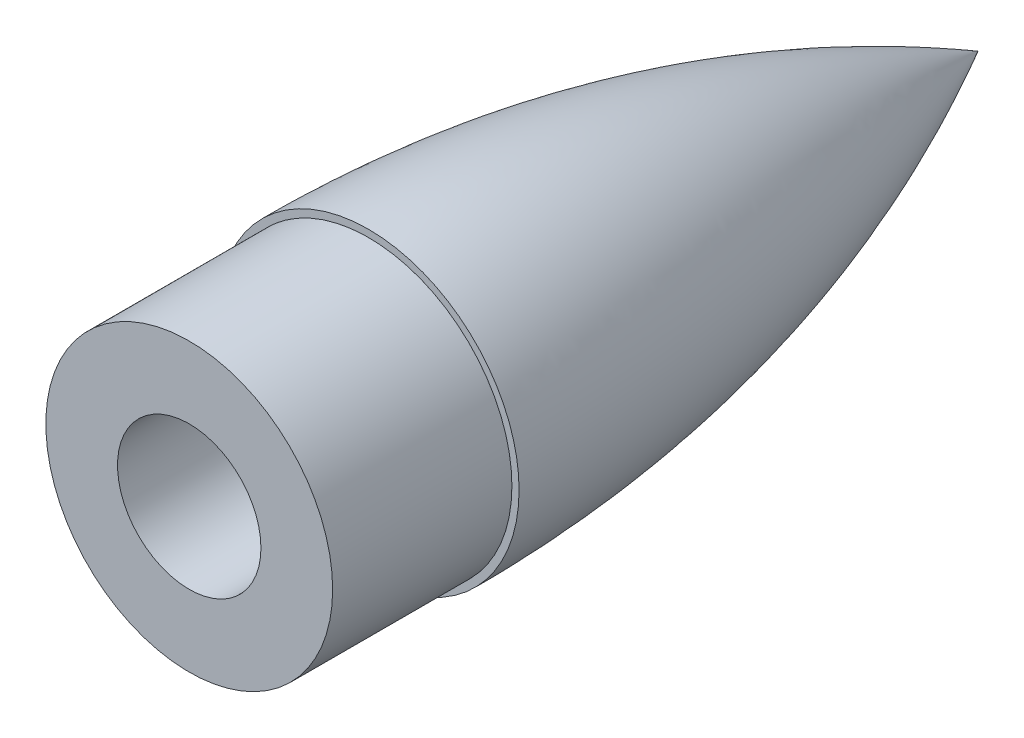
SolidWorks part; units mm, degrees
material "ABS"
ref_plane "Front Plane" through (0, 0, 0) normal (0, 0, 1) x (1, 0, 0)
ref_plane "Top Plane" through (0, 0, 0) normal (0, 1, 0) x (1, 0, 0)
ref_plane "Right Plane" through (0, 0, 0) normal (1, 0, 0) x (0, 0, -1)
sketch "Sketch1" plane through (0, 0, 0) normal (1, 0, 0) x (0, 0, -1)
  line L0 (-168, 0) -> (168, 0) construction
  line L1 (0, -42) -> (0, 42) construction
  line L2 (73.7564, 42) -> (-73.7564, 42) construction
  line L3 (72.8044, 40) -> (-72.8044, 40) construction
  line L4 (0, 40) -> (0, 42)
  line L5 (0, -40) -> (0, -42)
  line L6 (65.4024, 0) -> (-37.1775, 0)
  line L7 (168, 0) -> (170, 0)
  line L8 (0, 40) -> (23.6262, 40) construction
  spline S0 degree 2 poles (0, 42) (92.1954, 42) (170, 0) knots 0 0 0 1 1 1
  spline S1 degree 2 poles (0, -42) (92.1954, -42) (170, 0) knots 0 0 0 1 1 1
  spline S2 degree 2 poles (0, 40) (91.0055, 40) (168, 0) knots 0 0 0 1 1 1
  spline S3 degree 2 poles (0, -40) (91.0055, -40) (168, 0) knots 0 0 0 1 1 1
  point P0 (0, 40)
  point P4 (0, 0)
  point P7 (0, 0)
  point P9 (168, 0)
  dimension "D1" = 84
  dimension "D2" = 170
  dimension "D3" = 80
  dimension "D4" = 2
revolve "Revolve6" add sketch "Sketch1" angle 360 about L0 region at (0, 41, -1.7511)
sketch "Sketch2" [suppressed] plane through (0, 0, 0) normal (0, 0, 1) x (1, 0, 0)
  circle A0 centre (0, 0) radius 42 construction
  circle A3 centre (0, 0) radius 42
sketch "Sketch15" plane through (0, 0, 0) normal (1, 0, 0) x (0, 0, -1)
  line L3 (65.4024, 0) -> (-37.1775, 0) construction
  line L6 (0, 40) -> (0, 0)
  line L7 (168, 0) -> (0, 0)
  parabola Q1 (0, 40) -> (168, 0) focus (64.5986, -144.4227) apex (122.1376, 19.8455) construction
  parabola Q5 (0, 40) -> (168, 0) focus (64.5986, -144.4227) apex (122.1376, 19.8455)
  point P1 (60.2618, 0)
revolve "Revolve7" add sketch "Sketch15" angle 360 about L7
sketch "Sketch16" plane through (0, 0, 0) normal (1, 0, 0) x (0, 0, -1)
  line L0 (168, 0) -> (0, 0) construction
  line L1 (0, 40) -> (0, 0) construction
  line L2 (85, 0) -> (0, 0)
  line L3 (0, 40) -> (0, 0)
  line L4 (85, 30.5863) -> (85, 0)
  parabola Q0 (0, 40) -> (168, 0) focus (64.5986, -144.4227) apex (122.1376, 19.8455) construction
  parabola Q1 (0, 40) -> (85, 30.5863) focus (64.5986, -144.4227) apex (122.1376, 19.8455)
  dimension "D1" = 85
revolve "Cut-Revolve1" cut sketch "Sketch16" angle 360 about L2
sketch "Sketch18" plane through (0, 0, -85) normal (0, 0, 1) x (1, 0, 0)
  line L0 (0, -18) -> (0, 18) construction
  line L1 (-4.2842, 0) -> (4.2842, 0) construction
  line L2 (-10, 24) -> (10, 24)
  line L3 (-10, 24) -> (-10, 12)
  line L4 (-10, 12) -> (10, 12)
  line L5 (10, 24) -> (10, 12)
  line L6 (-10, 24) -> (10, 12) construction
  line L7 (-10, 12) -> (10, 24) construction
  line L8 (-10, -12) -> (10, -12)
  line L9 (10, -24) -> (10, -12)
  line L10 (-10, -24) -> (-10, -12)
  line L11 (-10, -24) -> (10, -24)
  circle A1 centre (0, 18) radius 5 construction
  circle A2 centre (-8, 18) radius 1.5 construction
  circle A3 centre (8, 18) radius 1.5 construction
  circle A4 centre (0, -18) radius 5 construction
  circle A5 centre (8, -18) radius 1.5 construction
  circle A6 centre (-8, -18) radius 1.5 construction
  point P0 (0, 0)
  point P12 (0, 0)
  dimension "D1" = 36
  dimension "D3" = 3
  dimension "D2" = 20
  dimension "D4" = 8
extrude "Boss-Extrude2" add sketch "Sketch18" along normal blind 10
sketch "Sketch19" plane through (0, 0, -75) normal (0, 0, 1) x (1, 0, 0)
  line L4 (10, 12) -> (10, 24)
  line L5 (10, 24) -> (-10, 24)
  line L6 (-10, 24) -> (-10, 12)
  line L7 (-10, 12) -> (10, 12)
  line L8 (10, 12) -> (10, 24)
  line L9 (10, 24) -> (-10, 24)
  line L10 (-10, 24) -> (-10, 12)
  line L11 (-10, 12) -> (10, 12)
  circle A0 centre (8, -18) radius 1.5 construction
  circle A1 centre (-8, -18) radius 1.5 construction
  circle A2 centre (8, 18) radius 1.5 construction
  circle A3 centre (-8, 18) radius 1.5 construction
  circle A4 centre (8, -18) radius 1.5
  circle A5 centre (-8, -18) radius 1.5
  circle A6 centre (8, 18) radius 1.5
  circle A7 centre (-8, 18) radius 1.5
  dimension "D1" = 0
extrude "Cut-Extrude1" cut sketch "Sketch19" against normal blind 15 contours A7 | A6 | A5 | A4 region at (8, -18, -75) region at (-8, -18, -75) region at (8, 18, -75) region at (-8, 18, -75)
sketch "Sketch20" plane through (0, 0, -75) normal (0, 0, 1) x (1, 0, 0)
  circle A0 centre (0, 18) radius 5 construction
  circle A1 centre (0, 18) radius 5
  circle A2 centre (0, -18) radius 5 construction
  circle A3 centre (0, -18) radius 5
sketch "Sketch22" plane through (0, 0, 0) normal (1, 0, 0) x (0, 0, -1)
  line L0 (75, 23) -> (75, 13) construction
  line L1 (75, -13) -> (75, -23) construction
  arc A0 (75, 18) -> (75, -18) centre (77.6352, 0) ccw
sweep "Sweep2" add path "Sketch22" circular profile diameter 10 parameters "D3"=10
sketch "Sketch30" plane through (0, 0, -85) normal (0, 0, 1) x (1, 0, 0)
  circle A1 centre (0, 0) radius 30.5863
  circle A5 centre (0, 0) radius 30.5863
  dimension "D1" = 0
extrude "Cut-Extrude2" [suppressed] cut sketch "Sketch30" along normal blind 76
sketch "Sketch43" plane through (0, 0, 0) normal (1, 0, 0) x (0, 0, -1)
  line L0 (65.4024, 0) -> (-37.1775, 0) construction
  line L1 (30, 0) -> (0, 0)
  line L2 (0, -42) -> (0, 42) construction
  line L3 (0, 0) -> (0, 40)
  line L4 (30, 0) -> (30, 38.8848)
  parabola Q0 (0, 40) -> (168, 0) focus (64.5986, -144.4227) apex (122.1376, 19.8455) construction
  parabola Q1 (0, 40) -> (30, 38.8848) focus (64.5986, -144.4227) apex (122.1376, 19.8455)
  dimension "D1" = 30
revolve "Revolve8" add sketch "Sketch43" angle 360 about L1
sketch "Sketch46" plane through (0, 0, 0) normal (0, 0, 1) x (1, 0, 0)
  circle A1 centre (0, 0) radius 40
  circle A2 centre (0, 0) radius 40
  dimension "D1" = 0
extrude "Boss-Extrude4" add sketch "Sketch46" along normal blind 50 separate body
sketch "Sketch47" plane through (0, 0, 50) normal (0, 0, 1) x (1, 0, 0)
  circle A0 centre (0, 0) radius 20
  circle A1 centre (0, 0) radius 40 construction
  dimension "D1" = 20
extrude "Cut-Extrude3" cut sketch "Sketch47" against normal up to surface (80 mm away) up to face at (0, 38.8848, -30)
